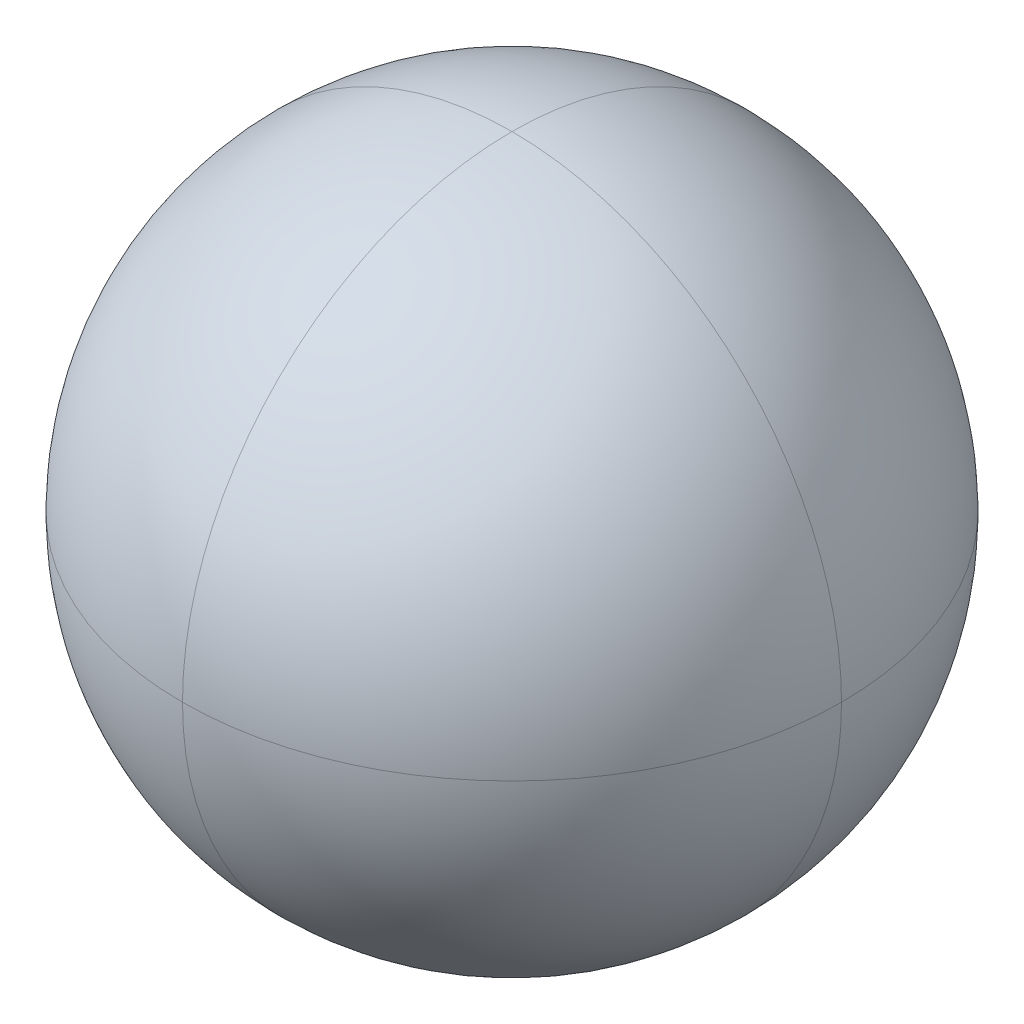
SolidWorks part; units mm, degrees
ref_plane "Front Plane" through (0, 0, 0) normal (0, 0, 1) x (1, 0, 0)
ref_plane "Top Plane" through (0, 0, 0) normal (0, 1, 0) x (1, 0, 0)
ref_plane "Right Plane" through (0, 0, 0) normal (1, 0, 0) x (0, 0, -1)
sketch "Sketch1" plane through (0, 0, 0) normal (0, 0, 1) x (1, 0, 0)
  line L1 (-26.4186, 10.2791) -> (13.5814, 10.2791)
  line L2 (-26.4186, 10.2791) -> (-26.4186, -29.7209)
  line L3 (-26.4186, -29.7209) -> (13.5814, -29.7209)
  line L4 (13.5814, 10.2791) -> (13.5814, -29.7209)
  dimension "D1" = 40
  dimension "D2" = 40
extrude "Boss-Extrude2" add sketch "Sketch1" along normal blind 40
fillet "Fillet4" radius 20 4 edges at (-6.4186, 10.2791, 40) (-26.4186, -9.7209, 40) (-6.4186, -29.7209, 40) (13.5814, -9.7209, 40)
fillet "Fillet5" radius 20 8 edges at (-26.4186, 10.2791, 10) (13.5814, -29.7209, 10) (-26.4186, -29.7209, 10) (13.5814, 10.2791, 10) (7.7235, 4.4212, 34.1421) (-20.5607, 4.4212, 34.1421) (7.7235, -23.8631, 34.1421) (-20.5607, -23.8631, 34.1421)
fillet "Fillet6" radius 20 4 edges at (7.7235, -23.8631, 0) (7.7235, 4.4212, 0) (-20.5607, 4.4212, 0) (-20.5607, -23.8631, 0)
